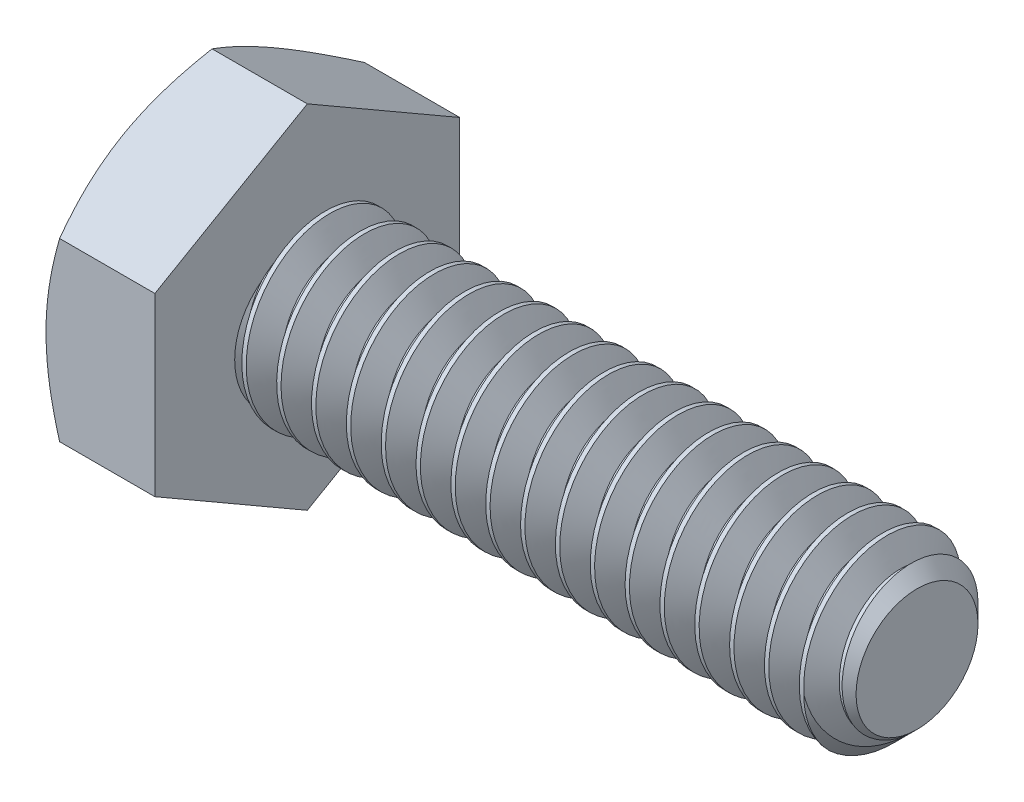
SolidWorks part; units mm, degrees
material "AISI Type 316L stainless steel"
ref_plane "Front Plane" through (0, 0, 0) normal (0, 0, 1) x (1, 0, 0)
ref_plane "Top Plane" through (0, 0, 0) normal (0, 1, 0) x (1, 0, 0)
ref_plane "Right Plane" through (0, 0, 0) normal (1, 0, 0) x (0, 0, -1)
sketch "Sketch1" plane through (0, 0, 0) normal (0, 0, 1) x (1, 0, 0)
  line L0 (-13.0969, 0) -> (13.0969, 0) construction
  line L1 (13.0969, 3.175) -> (13.0969, -3.175) construction
  line L2 (-9.1281, 5.5562) -> (-9.1281, -5.5562) construction
  line L3 (-13.0969, 5.5562) -> (-13.0969, -5.5562) construction
  point P9 (-9.1281, 0)
  point P10 (8.6519, -3.175)
  dimension "D1" = 4.445
  dimension "Screw Dia" = 6.35
  dimension "Hex" = 11.1125
  dimension "Head Ht" = 3.9688
  dimension "Screw Lenght" = 22.225
ref_plane "Plane2" through (13.0969, 0, 0) normal (1, 0, 0) x (0, 0, -1)
sketch "Sketch5" plane through (13.0969, 0, 0) normal (1, 0, 0) x (0, 0, -1)
  circle A0 centre (0, 0) radius 3.175
extrude "Boss-Extrude3" add sketch "Sketch5" against normal up to vertex (22.225 mm away) up to point (-9.1281, 0, 0)
sketch "Sketch9" plane through (13.0969, 0, 0) normal (1, 0, 0) x (0, 0, -1)
  circle A1 centre (0, 0) radius 3.175
  circle A2 centre (0, 0) radius 3.175
  dimension "D1" = 0
curve "Helix/Spiral1" pitch 1.27 height 23.495 turns 18.5 parameters "Pitch"=1.27
chamfer "Chamfer1" distance 0.9525 angle 45 1 edges at (13.0969, 0, -3.175)
sketch "Sketch10" plane through (0, 0, 0) normal (0, 0, 1) x (1, 0, 0)
  line L0 (13.0969, 3.175) -> (13.5731, 2.3501)
  line L1 (13.5731, 2.3501) -> (13.7319, 2.3501)
  line L2 (13.7319, 2.3501) -> (14.2081, 3.175)
  line L3 (13.0969, 3.175) -> (14.2081, 3.175)
  line L4 (13.6525, 3.175) -> (13.6525, 2.3501) construction
  line L5 (13.335, 2.7626) -> (13.97, 2.7626) construction
  dimension "D1" = 60
  dimension "D2" = 0.1588
  dimension "D3" = 0.635
sweep "Cut-Sweep1" cut profiles "Sketch10" path "Helix/Spiral1" align with end faces yes
sketch "Sketch6" plane through (-9.1281, 0, 0) normal (-1, 0, 0) x (0, 0, 1)
  line L0 (0, 5.5562) -> (0, -5.5562) construction
  line L1 (5.5562, 3.2079) -> (0, 6.4158)
  line L2 (0, 6.4158) -> (-5.5562, 3.2079)
  line L3 (-5.5562, 3.2079) -> (-5.5562, -3.2079)
  line L4 (-5.5562, -3.2079) -> (0, -6.4158)
  line L5 (0, -6.4158) -> (5.5562, -3.2079)
  line L6 (5.5562, -3.2079) -> (5.5562, 3.2079)
  circle A0 centre (0, 0) radius 5.5562 construction
extrude "Boss-Extrude4" add sketch "Sketch6" along normal up to vertex (3.9688 mm away) up to point (-13.0969, -5.5562, 0)
sketch "Sketch7" plane through (-13.0969, 0, 0) normal (-1, 0, 0) x (0, 0, 1)
  circle A0 centre (0, 0) radius 5.5562 construction
  circle A1 centre (0, 0) radius 5.5562
sketch "Sketch8" plane through (-13.0969, 0, 0) normal (-1, 0, 0) x (0, 0, 1)
  circle A0 centre (0, 0) radius 5.5562 construction
  circle A1 centre (0, 0) radius 5.5562
extrude "Cut-Extrude3" cut sketch "Sketch8" against normal through all draft 60 flip side to cut
equation "\"D2@Sketch10\" = \"Pitch@Helix/Spiral1\"*.125"
equation "\"D3@Sketch10\" = \"Pitch@Helix/Spiral1\"*.5"
equation "\"D3@Helix/Spiral1\" = \"Screw Lenght@Sketch1\"+\"Pitch@Helix/Spiral1\""
equation "\"D1@Chamfer1\" = \"Pitch@Helix/Spiral1\"*.75"
equation "\"D1@Sketch1\" = \"Pitch@Helix/Spiral1\"*3.5"
